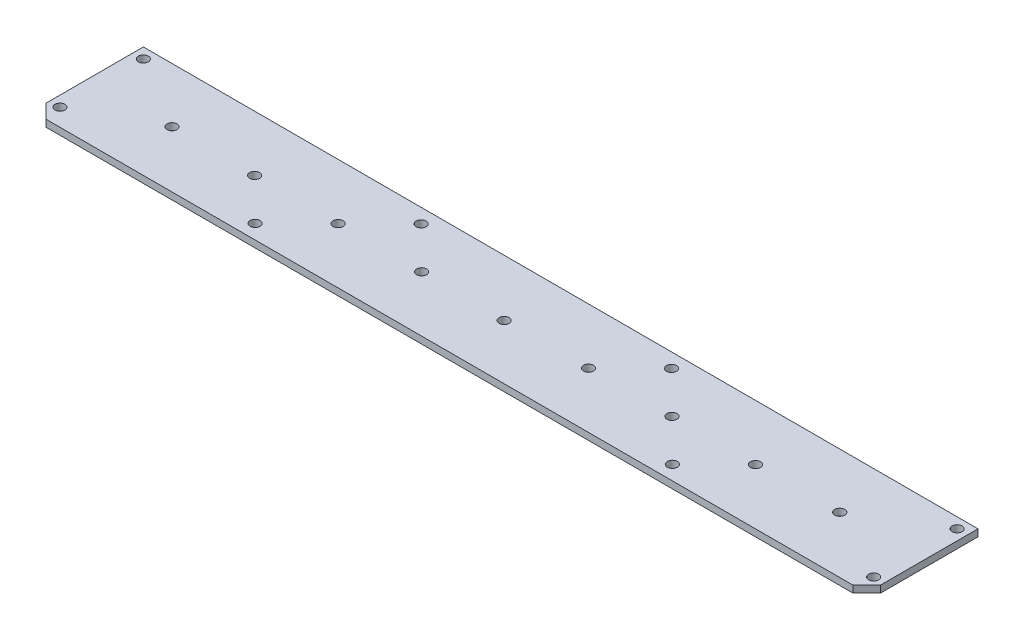
SolidWorks part; units mm, degrees
ref_plane "Front Plane" through (0, 0, 0) normal (0, 0, 1) x (1, 0, 0)
ref_plane "Top Plane" through (0, 0, 0) normal (0, 1, 0) x (1, 0, 0)
ref_plane "Right Plane" through (0, 0, 0) normal (1, 0, 0) x (0, 0, -1)
sketch "Sketch2" plane through (0, 0, 0) normal (0, 1, 0) x (1, 0, 0)
  line L0 (0, 0) -> (0, 50.8)
  line L1 (0, 50.8) -> (381, 50.8)
  line L2 (381, 50.8) -> (381, 0)
  line L3 (381, 0) -> (0, 0)
  dimension "D1" = 50.8
  dimension "D2" = 381
extrude "Boss-Extrude1" add sketch "Sketch2" along normal blind 3.175
sketch "Sketch3" plane through (0, 3.175, 0) normal (0, 1, 0) x (1, 0, 0)
  line L0 (190.5, 0) -> (190.5, 50.8) construction
  line L1 (0, 0) -> (381, 0) construction
  line L2 (381, 50.8) -> (0, 50.8) construction
  line L3 (38.1, 25.7969) -> (190.5, 25.0031) construction
  line L4 (342.9, 25.7969) -> (190.5, 25.0031) construction
  line L5 (0, 6.35) -> (6.35, 0)
  line L6 (6.35, 0) -> (0, 0)
  line L7 (0, 0) -> (0, 6.35)
  line L8 (374.65, 0) -> (381, 0)
  line L9 (381, 6.35) -> (374.65, 0)
  line L10 (381, 0) -> (381, 6.35)
  line L11 (247.65, 44.2526) -> (285.75, 6.5474) construction
  line L12 (0, 50.8) -> (0, 0) construction
  circle A0 centre (190.5, 25.0031) radius 2.286
  circle A1 centre (38.1, 25.7969) radius 2.286
  circle A2 centre (114.3, 25.4) radius 2.286
  circle A3 centre (76.2, 25.4) radius 2.286
  circle A4 centre (152.4, 25.4) radius 2.286
  circle A5 centre (228.6, 25.4) radius 2.286
  circle A6 centre (304.8, 25.4) radius 2.286
  circle A7 centre (266.7, 25.4) radius 2.286
  circle A8 centre (342.9, 25.7969) radius 2.286
  circle A9 centre (247.65, 44.2526) radius 2.286
  circle A10 centre (285.75, 6.5474) radius 2.286
  circle A11 centre (95.25, 6.5474) radius 2.286
  circle A12 centre (133.35, 44.2526) radius 2.286
  circle A13 centre (4.7625, 46.0375) radius 2.286
  circle A14 centre (4.7625, 7.9375) radius 2.286
  circle A15 centre (376.2375, 7.9375) radius 2.286
  circle A16 centre (376.2375, 46.0375) radius 2.286
  point P37 (266.7, 25.4)
  point P44 (0, 0)
  dimension "D1" = 4.572
  dimension "D2" = 0.7937
  dimension "D6" = 25.4
  dimension "D11" = 4.7625
  dimension "D14" = 4.572
  dimension "D3" = 152.4
  dimension "D4" = 38.1
  dimension "D5" = 38.1
  dimension "D7" = 6.35
  dimension "D8" = 6.35
  dimension "D9" = 45
  dimension "D10" = 19.05
  dimension "D12" = 4.7625
  dimension "D13" = 7.9375
extrude "Cut-Extrude1" cut sketch "Sketch3" against normal up to next
